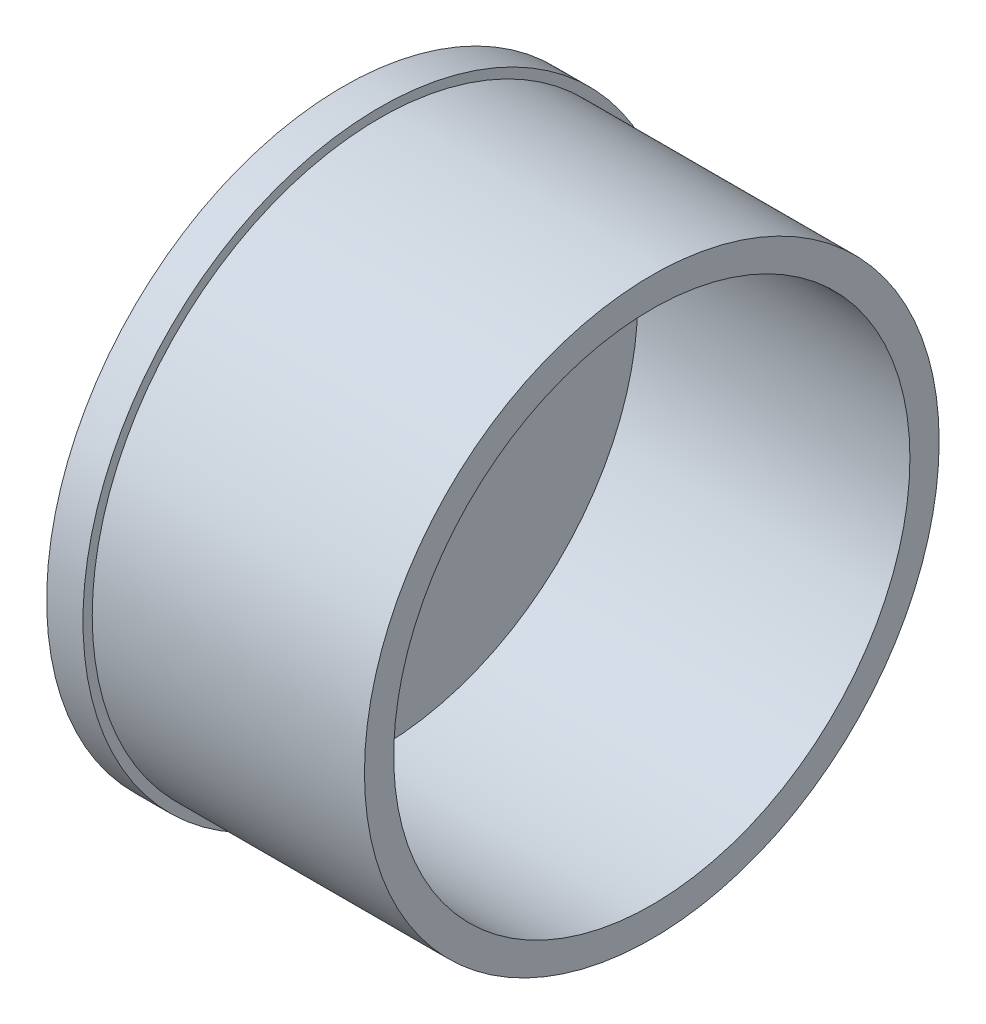
SolidWorks part; units mm, degrees
ref_plane "Front Plane" through (0, 0, 0) normal (1, 0, 0) x (0, 1, 0)
ref_plane "Top Plane" through (0, 0, 0) normal (0, 0, 1) x (0, 1, 0)
ref_plane "Right Plane" through (0, 0, 0) normal (0, 1, 0) x (-1, 0, 0)
sketch "Sketch1" plane through (0, 0, 0) normal (0, 0, 1) x (0, 1, 0)
  line L0 (0, 0) -> (0, 25.8273) construction
  line L1 (10, 6) -> (10, 0)
  line L2 (10, 0) -> (49.03, 0)
  line L4 (10, 6) -> (49.03, 6)
  line L5 (49.03, 0) -> (49.03, 6)
  line L6 (47.5, 0) -> (42.6688, 0)
  line L7 (47.5, 0) -> (47.5, -45)
  line L8 (47.5, -45) -> (42.6688, -45)
  line L9 (42.6688, 0) -> (42.6688, -45)
  dimension "D1" = 6
  dimension "D2" = 39.03
  dimension "D3" = 45
  dimension "D4" = 1.53
  dimension "D5" = 49.03
revolve "Revolve1" add sketch "Sketch1" angle 360 about L0 region at (-3, 29.515, 0)
